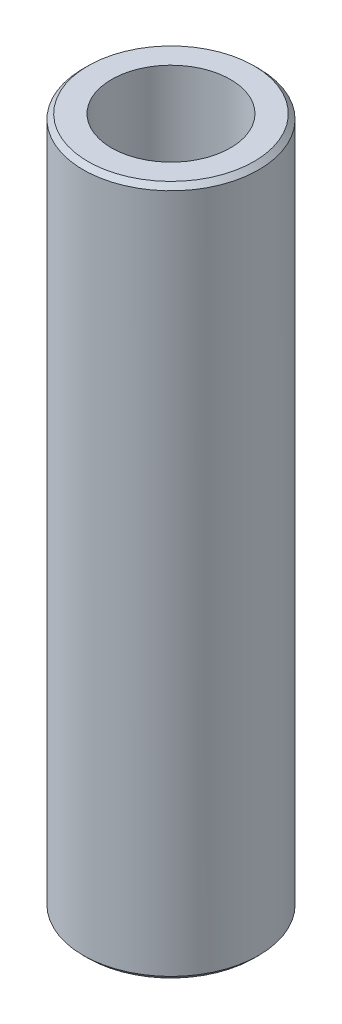
SolidWorks part; units mm, degrees
ref_plane "Front Plane" through (0, 0, 0) normal (0, 0, 1) x (1, 0, 0)
ref_plane "Top Plane" through (0, 0, 0) normal (0, 1, 0) x (1, 0, 0)
ref_plane "Right Plane" through (0, 0, 0) normal (1, 0, 0) x (0, 0, -1)
sketch "Sketch1" plane through (0, 0, 0) normal (0, 1, 0) x (1, 0, 0)
  circle A0 centre (0, 0) radius 35
  dimension "SHAFT_OD" = 70
extrude "Boss-Extrude1" add sketch "Sketch1" along normal blind 275.2035
sketch "Sketch2" plane through (0, 0, 0) normal (0, 1, 0) x (1, 0, 0)
  circle A0 centre (0, 0) radius 23.6992
  dimension "BORE_D" = 47.3984
extrude "Cut-Extrude1" cut sketch "Sketch2" along normal through all
chamfer "Chamfer1" distance 1.9017 angle 45 2 edges at (0, 275.2035, 35) (0, 0, 35)
